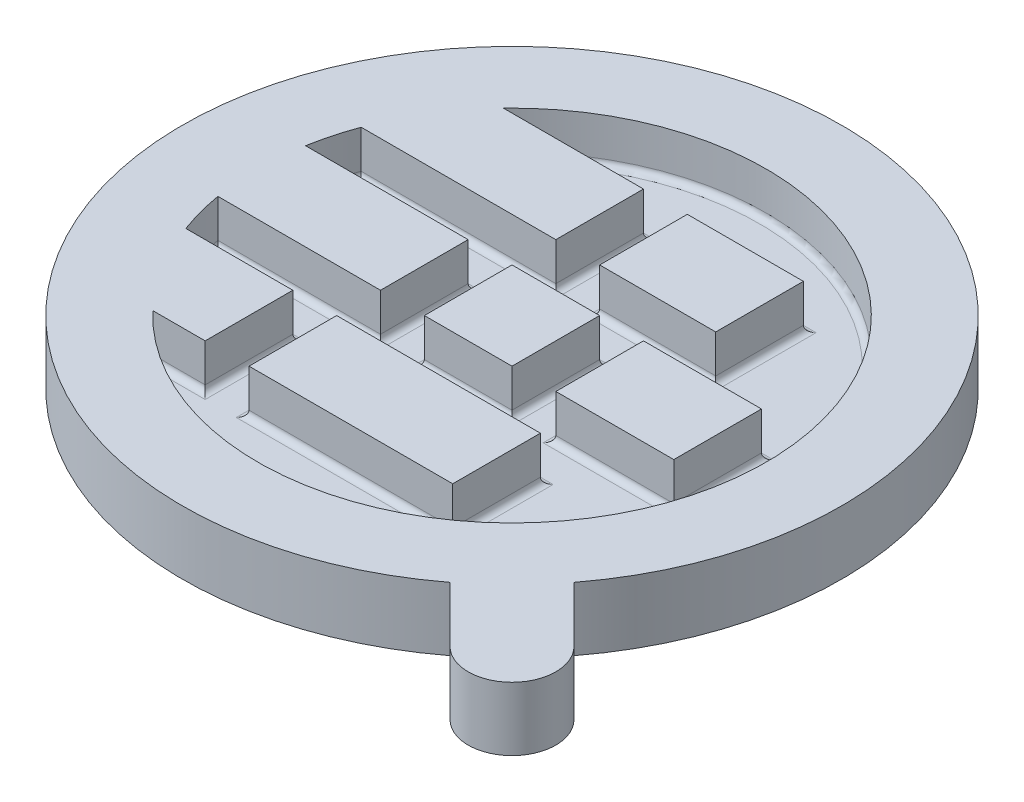
SolidWorks part; units mm, degrees
ref_plane "Front Plane" through (0, 0, 0) normal (0, 0, 1) x (1, 0, 0)
ref_plane "Top Plane" through (0, 0, 0) normal (0, 1, 0) x (1, 0, 0)
ref_plane "Right Plane" through (0, 0, 0) normal (1, 0, 0) x (0, 0, -1)
sketch "Sketch1" plane through (0, 0, 0) normal (0, 1, 0) x (1, 0, 0)
  line L0 (100, 100) -> (0, 0) construction
  line L1 (0, 0) -> (100, 0) construction
  line L2 (0, 0) -> (0, 100) construction
  line L3 (0, 100) -> (100, 100) construction
  line L5 (0, 100) -> (100, 0) construction
  line L6 (100, 9.7581) -> (78.7868, 30.9713)
  line L7 (90.2419, 0) -> (69.0287, 21.2132)
  line L8 (100, 9.7581) -> (90.2419, 0)
  line L9 (78.7868, 30.9713) -> (69.0287, 21.2132) construction
  line L10 (50, 50) -> (0, 50) construction
  line L11 (43.1, 56.9) -> (56.9, 56.9)
  line L12 (43.1, 56.9) -> (43.1, 43.1)
  line L13 (43.1, 43.1) -> (56.9, 43.1)
  line L14 (56.9, 56.9) -> (56.9, 43.1)
  line L15 (43.1, 56.9) -> (56.9, 43.1) construction
  line L16 (43.1, 43.1) -> (56.9, 56.9) construction
  line L17 (70.7, 29.3) -> (0, 29.3) construction
  line L18 (10, 56.9) -> (36.2, 56.9)
  line L19 (10, 56.9) -> (10, 43.1)
  line L20 (10, 43.1) -> (36.2, 43.1)
  line L21 (36.2, 56.9) -> (36.2, 43.1)
  line L22 (10, 56.9) -> (36.2, 43.1) construction
  line L23 (10, 43.1) -> (36.2, 56.9) construction
  line L24 (70.7, 70.7) -> (0, 70.7) construction
  line L25 (50, 50) -> (50, 100) construction
  line L26 (12.4559, 77.6) -> (43.1, 77.6)
  line L27 (12.4559, 77.6) -> (12.4559, 63.8)
  line L28 (12.4559, 63.8) -> (43.1, 63.8)
  line L29 (43.1, 77.6) -> (43.1, 63.8)
  line L30 (12.4559, 77.6) -> (43.1, 63.8) construction
  line L31 (12.4559, 63.8) -> (43.1, 77.6) construction
  line L32 (50, 50) -> (100, 50) construction
  line L33 (50, 77.6) -> (68.27, 77.6)
  line L34 (50, 77.6) -> (50, 63.8)
  line L35 (50, 63.8) -> (68.27, 63.8)
  line L36 (68.27, 77.6) -> (68.27, 63.8)
  line L37 (50, 77.6) -> (68.27, 63.8) construction
  line L38 (50, 63.8) -> (68.27, 77.6) construction
  line L40 (63.8, 56.9) -> (82.37, 56.9)
  line L41 (63.8, 56.9) -> (63.8, 43.1)
  line L42 (63.8, 43.1) -> (82.37, 43.1)
  line L43 (82.37, 56.9) -> (82.37, 43.1)
  line L44 (63.8, 56.9) -> (82.37, 43.1) construction
  line L45 (63.8, 43.1) -> (82.37, 56.9) construction
  line L46 (12.4559, 36.2) -> (29.3, 36.2)
  line L47 (12.4559, 36.2) -> (12.4559, 22.4)
  line L48 (12.4559, 22.4) -> (29.3, 22.4)
  line L49 (29.3, 36.2) -> (29.3, 22.4)
  line L50 (12.4559, 36.2) -> (29.3, 22.4) construction
  line L51 (12.4559, 22.4) -> (29.3, 36.2) construction
  line L52 (36.2, 36.2) -> (68.27, 36.2)
  line L53 (36.2, 36.2) -> (36.2, 22.4)
  line L54 (36.2, 22.4) -> (68.27, 22.4)
  line L55 (68.27, 36.2) -> (68.27, 22.4)
  line L56 (36.2, 36.2) -> (68.27, 22.4) construction
  line L57 (36.2, 22.4) -> (68.27, 36.2) construction
  circle A0 centre (50, 50) radius 50
  arc A1 (100, 9.7581) -> (90.2419, 0) centre (95.121, 4.879) cw
  circle A2 centre (50, 50) radius 40
  circle A3 centre (68.27, 77.6) radius 6.9009 construction
  circle A4 centre (82.37, 56.9) radius 6.9028 construction
  circle A5 centre (68.27, 22.4) radius 6.9009 construction
  circle A6 centre (50, 50) radius 51.9
  point P19 (23.1, 50)
  point P29 (27.7779, 70.7)
  point P34 (59.135, 70.7)
  point P40 (73.085, 50)
  point P46 (20.8779, 29.3)
  point P52 (52.235, 29.3)
  dimension "D5" = 30
  dimension "D12" = 20.7
  dimension "D24" = 6.9009
  dimension "D25" = 6.9028
  dimension "D27" = 11.9
  dimension "D1" = 100
  dimension "D2" = 100
  dimension "D3" = 6.9
  dimension "D4" = 6.9
  dimension "D7" = 13.8
  dimension "D8" = 13.8
  dimension "D9" = 13.8
  dimension "D10" = 26.2
  dimension "D11" = 6.9
  dimension "D13" = 20.7
  dimension "D14" = 13.8
  dimension "D15" = 13.8
  dimension "D16" = 18.27
  dimension "D17" = 6.9
  dimension "D18" = 13.8
  dimension "D19" = 6.9
  dimension "D20" = 18.57
  dimension "D21" = 13.8
  dimension "D22" = 6.9
  dimension "D23" = 13.8
  dimension "D26" = 6.9009
  dimension "D6" = 10
extrude "Boss-Extrude12" add sketch "Sketch1" along normal blind 3 contours A2 L18 L19 | A2 L19 L20 | A2 L27 L26 L6 A0 L7 L48 L47 L20 L19 L18 | A2 L26 L27 | L18 A2 L20 L21 | L46 A2 L48 L49 | A2 L47 L48 | L26 A2 L28 L29 | L36 L33 L34 L35 | L43 L40 L41 L42 | L14 L11 L12 L13 | L55 L52 L53 L54 | A2 L7 A0 L6 | A0 L7 L8 L6 | A1 L8 | L28 A2 L18 L21 L20 L46 L49 L48 L26 L29 L52 L55 L54 L53 L40 L43 L42 L41 L33 L36 L35 L34 L11 L14 L13 L12 | L6 A6 L7 A0 | L7 A6 L6 A0 region at (90.8552, 0, -9.1448) region at (97.1917, 0, -2.8083) region at (85.9163, 0, -14.0837) region at (91.6121, 0, -20.222) region at (81.6927, 0, -18.3073) region at (87.3177, 0, -24.4404) region at (77.4873, 0, -22.5127) region at (22.4668, 0, -30.0395) region at (15.1126, 0, -26.6168) region at (15.1126, 0, -73.3832) region at (29.4847, 0, -70.3384) region at (23.199, 0, -50) region at (10.1797, 0, -44.8224) region at (10.1797, 0, -55.1776) region at (50, 0, -50) region at (59.135, 0, -70.7) region at (73.085, 0, -50) region at (52.235, 0, -29.3)
extrude "Boss-Extrude13" add sketch "Sketch1<16>" along normal blind 10 contours A2 L27 L26 L6 A0 L7 L48 L47 L20 L19 L18 | A2 L26 L27 | A2 L18 L19 | A2 L19 L20 | L18 A2 L20 L21 | L26 A2 L28 L29 | L36 L33 L34 L35 | L46 A2 L48 L49 | A2 L47 L48 | L55 L52 L53 L54 | L43 L40 L41 L42 | A2 L7 A0 L6 | A0 L7 L8 L6 | A1 L8 | L6 A6 L7 A0 | L7 A6 L6 A0 region at (90.8552, 0, -9.1448) region at (97.1917, 0, -2.8083) region at (85.9163, 0, -14.0837) region at (91.6121, 0, -20.222) region at (81.6927, 0, -18.3073) region at (87.3177, 0, -24.4404) region at (22.4668, 0, -30.0395) region at (15.1126, 0, -26.6168) region at (15.1126, 0, -73.3832) region at (29.4847, 0, -70.3384) region at (23.199, 0, -50) region at (10.1797, 0, -44.8224) region at (10.1797, 0, -55.1776) region at (59.135, 0, -70.7) region at (73.085, 0, -50) region at (52.235, 0, -29.3)
sketch "Sketch1<16>" plane through (0, 0, 0) normal (0, 1, 0) x (1, 0, 0) same geometry as "Sketch1"
extrude "Boss-Extrude14" add sketch "Sketch1<17>" along normal blind 10 contours L11 L14 L13 L12
sketch "Sketch1<17>" plane through (0, 0, 0) normal (0, 1, 0) x (1, 0, 0) same geometry as "Sketch1"
fillet "Fillet1" radius 1 28 edges at (90, 3, -50) (36.2, 3, -29.3) (52.235, 3, -22.4) (50, 3, -70.7) (59.135, 3, -63.8) (43.1, 3, -50) (50, 3, -43.1) (63.8, 3, -50) (73.085, 3, -43.1) (50, 3, -56.9) (73.085, 3, -56.9) (56.9, 3, -50) (52.235, 3, -36.2) (68.27, 3, -29.3) (82.37, 3, -50) (68.27, 3, -70.7) (59.135, 3, -77.6) (32.0738, 3, -77.6) (43.1, 3, -70.7) (27.7779, 3, -63.8) (11.3734, 3, -60.3915) (23.3998, 3, -56.9) (36.2, 3, -50) (23.3998, 3, -43.1) (11.3734, 3, -39.6085) (20.8779, 3, -36.2) (29.3, 3, -29.3) (25.1738, 3, -22.4)
